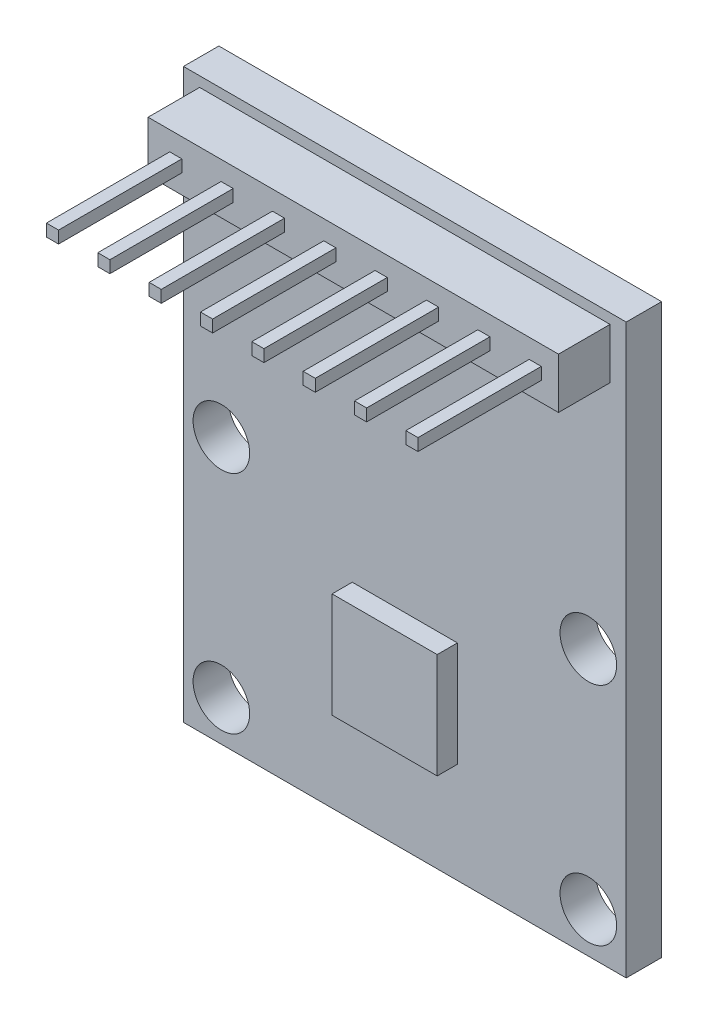
SolidWorks part; units mm, degrees
ref_plane "Front Plane" through (0, 0, 0) normal (0, 0, 1) x (1, 0, 0)
ref_plane "Top Plane" through (0, 0, 0) normal (0, 1, 0) x (1, 0, 0)
ref_plane "Right Plane" through (0, 0, 0) normal (1, 0, 0) x (0, 0, -1)
sketch "Sketch1" plane through (0, 0, 0) normal (0, 0, 1) x (1, 0, 0)
  line L1 (-10.95, -14.05) -> (10.95, -14.05)
  line L2 (-10.95, -14.05) -> (-10.95, 14.05)
  line L3 (-10.95, 14.05) -> (10.95, 14.05)
  line L4 (10.95, -14.05) -> (10.95, 14.05)
  line L5 (-10.95, -14.05) -> (10.95, 14.05) construction
  line L6 (-10.95, 14.05) -> (10.95, -14.05) construction
  point P0 (0, 0)
  dimension "D1" = 21.9
  dimension "D2" = 28.1
extrude "Boss-Extrude1" add sketch "Sketch1" along normal blind 1.75
sketch "Sketch2" plane through (0, 0, 1.75) normal (0, 0, 1) x (1, 0, 0)
  line L0 (-9.075, -0.89) -> (9.075, -12.05) construction
  line L1 (-9.075, -12.05) -> (9.075, -12.05) construction
  line L2 (-9.075, -12.05) -> (-9.075, -0.89) construction
  line L3 (-9.075, -0.89) -> (9.075, -0.89) construction
  line L4 (9.075, -12.05) -> (9.075, -0.89) construction
  line L5 (-10.95, -14.05) -> (10.95, -14.05) construction
  circle A0 centre (-9.075, -0.89) radius 1.4
  circle A1 centre (9.075, -0.89) radius 1.4
  circle A2 centre (9.075, -12.05) radius 1.4
  circle A3 centre (-9.075, -12.05) radius 1.4
  point P4 (0, -6.47)
  dimension "D4" = 2.8
  dimension "D1" = 18.15
  dimension "D2" = 11.16
  dimension "D3" = 2
extrude "Cut-Extrude1" cut sketch "Sketch2" against normal through all
sketch "Sketch3" plane through (0, 0, 1.75) normal (0, 0, 1) x (1, 0, 0)
  line L0 (-9.075, -0.89) -> (9.075, -12.05) construction
  line L2 (-2.6, -9.07) -> (2.6, -9.07)
  line L3 (-2.6, -9.07) -> (-2.6, -3.87)
  line L4 (-2.6, -3.87) -> (2.6, -3.87)
  line L5 (2.6, -9.07) -> (2.6, -3.87)
  line L6 (-2.6, -9.07) -> (2.6, -3.87) construction
  line L7 (-2.6, -3.87) -> (2.6, -9.07) construction
  point P4 (0, -6.47)
  dimension "D1" = 5.2
  dimension "D2" = 5.2
extrude "Boss-Extrude2" add sketch "Sketch3" along normal blind 1
sketch "Sketch4" plane through (0, 0, 1.75) normal (0, 0, 1) x (1, 0, 0)
  line L0 (10.95, 14.05) -> (-10.95, 14.05) construction
  line L1 (10.15, 13.55) -> (-10.15, 13.55)
  line L2 (10.15, 13.55) -> (10.15, 11.05)
  line L3 (10.15, 11.05) -> (-10.15, 11.05)
  line L4 (-10.15, 13.55) -> (-10.15, 11.05)
  line L5 (10.15, 13.55) -> (-10.15, 11.05) construction
  line L6 (10.15, 11.05) -> (-10.15, 13.55) construction
  point P0 (0, 12.3)
  dimension "D1" = 2.5
  dimension "D2" = 20.3
  dimension "D4" = 0.5
extrude "Boss-Extrude3" add sketch "Sketch4" along normal offset from surface (2.55 mm away) 4.3 up to face at (10.475, -0.89, 0)
sketch "Sketch5" plane through (0, 0, 4.3) normal (0, 0, 1) x (1, 0, 0)
  line L0 (-8.78, 13.55) -> (-8.78, 11.05) construction
  line L1 (-9.08, 12) -> (-8.48, 12)
  line L2 (-9.08, 12) -> (-9.08, 12.6)
  line L3 (-9.08, 12.6) -> (-8.48, 12.6)
  line L4 (-8.48, 12) -> (-8.48, 12.6)
  line L5 (-9.08, 12) -> (-8.48, 12.6) construction
  line L6 (-9.08, 12.6) -> (-8.48, 12) construction
  line L7 (10.15, 13.55) -> (-10.15, 13.55) construction
  line L8 (-10.15, 11.05) -> (10.15, 11.05) construction
  line L9 (-10.15, 11.05) -> (-10.15, 13.55) construction
  point P0 (-8.78, 12.3)
  point P11 (-8.78, 12.3)
  dimension "D1" = 0.6
  dimension "D2" = 1.37
extrude "Boss-Extrude4" add sketch "Sketch5" along normal offset from surface (6.1 mm away) 10.4 up to face at (10.475, -0.89, 0)
pattern_linear "LPattern1" count 8 spacing 2.54 along (1, 0, 0) of "Boss-Extrude4"
ref_point "Point1"
ref_axis "Axis1" through (0, -6.47, -8.1252) along (0, 0, 1)
